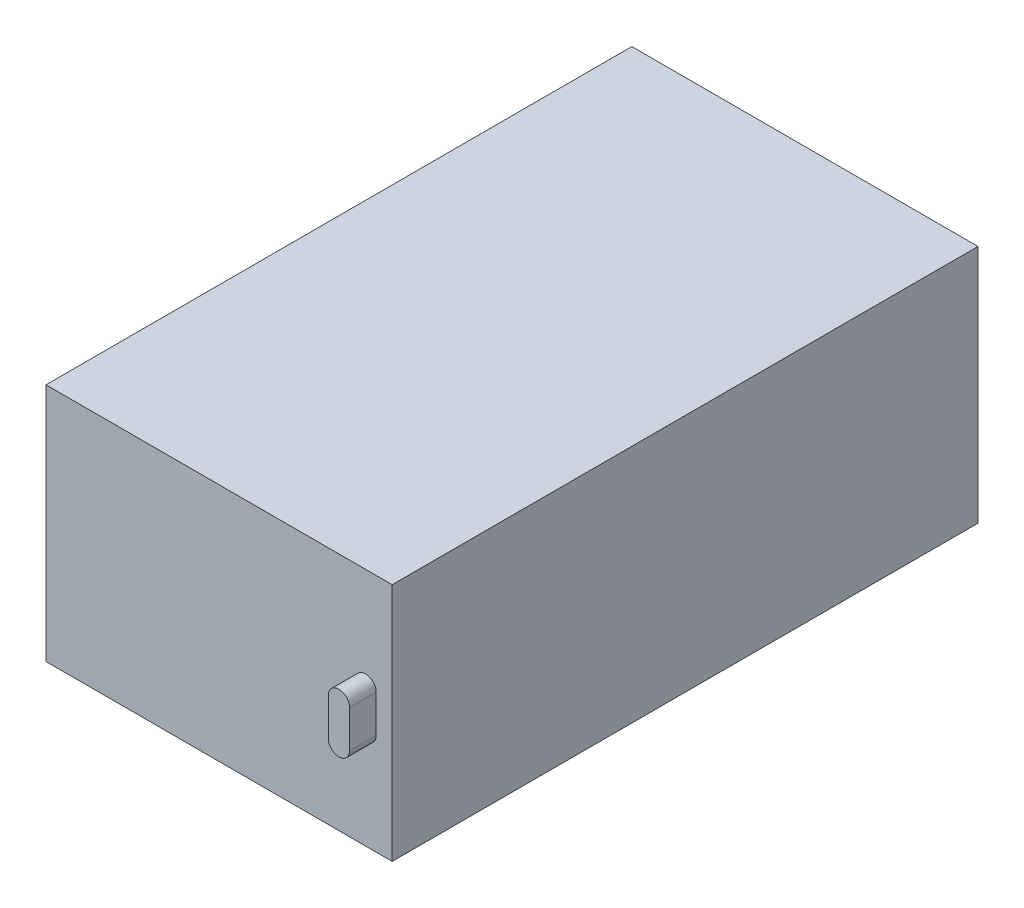
SolidWorks part; units mm, degrees
ref_plane "Front" through (0, 0, 0) normal (0, 0, 1) x (1, 0, 0)
ref_plane "Top" through (0, 0, 0) normal (0, 1, 0) x (1, 0, 0)
ref_plane "Right" through (0, 0, 0) normal (1, 0, 0) x (0, 0, -1)
sketch "Эскиз1" plane through (0, 0, 0) normal (1, 0, 0) x (0, 0, -1)
  line L0 (0, 0) -> (0, 90)
  line L1 (0, 90) -> (220, 90)
  line L2 (220, 90) -> (220, 0)
  line L3 (220, 0) -> (0, 0)
  dimension "D1" = 90
  dimension "D2" = 220
extrude "Бобышка-Вытянуть1" add sketch "Эскиз1" against normal blind 130
sketch "Эскиз2" plane through (0, 0, 0) normal (0, 0, 1) x (1, 0, 0)
  line L0 (-130, 45) -> (0, 45) construction
  line L1 (-130, 90) -> (-130, 0) construction
  line L2 (0, 90) -> (0, 0) construction
  line L3 (-10, 38) -> (-10, 52) construction
  line L4 (-14, 38) -> (-14, 52)
  line L5 (-6, 38) -> (-6, 52)
  arc A0 (-14, 38) -> (-6, 38) centre (-10, 38) ccw
  arc A1 (-6, 52) -> (-14, 52) centre (-10, 52) ccw
  point P8 (-10, 45)
  dimension "D1" = 8
  dimension "D2" = 14
  dimension "D3" = 10
extrude "Бобышка-Вытянуть2" add sketch "Эскиз2" along normal blind 10
